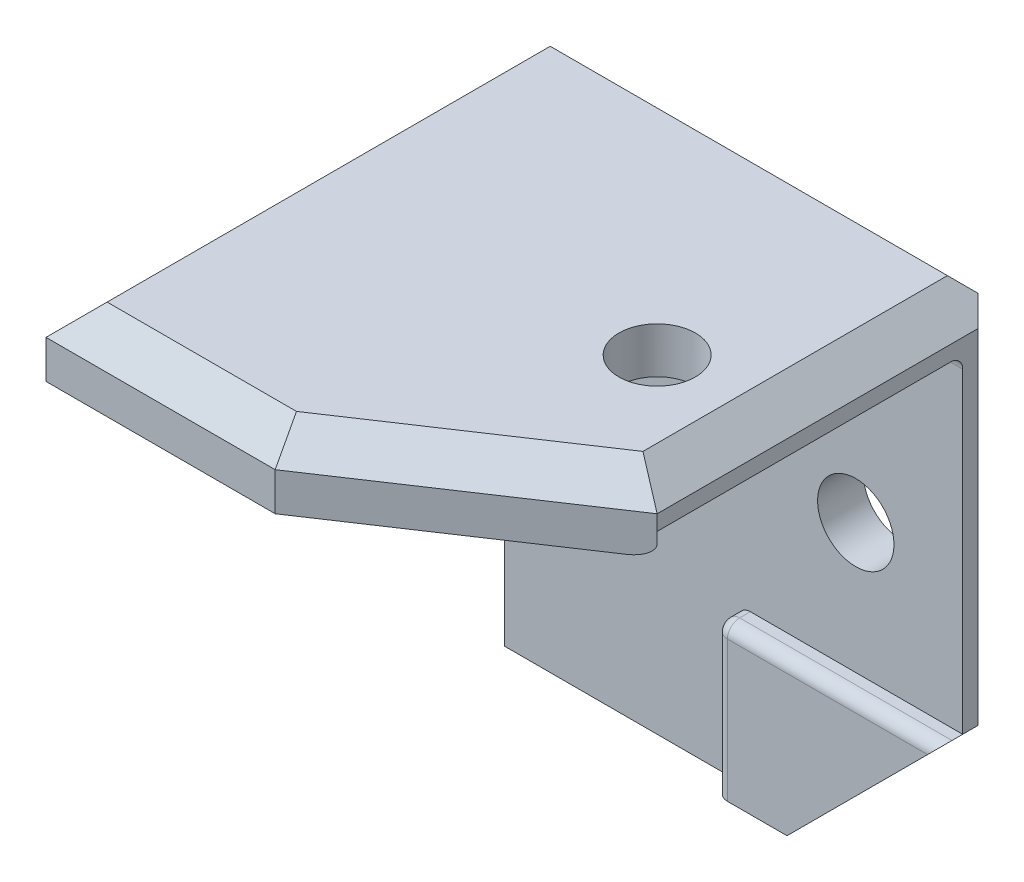
SolidWorks part; units mm, degrees
ref_plane "Front Plane" through (0, 0, 0) normal (0, 0, 1) x (1, 0, 0)
ref_plane "Top Plane" through (0, 0, 0) normal (0, 1, 0) x (1, 0, 0)
ref_plane "Right Plane" through (0, 0, 0) normal (1, 0, 0) x (0, 0, -1)
sketch "Sketch1" plane through (0, 0, 0) normal (0, 0, 1) x (1, 0, 0)
  line L0 (0, 0) -> (20, 0)
  line L1 (20, 0) -> (30, 10)
  line L2 (30, 10) -> (30, 30)
  line L3 (30, 30) -> (0, 30)
  line L4 (0, 30) -> (0, 0)
  dimension "D1" = 20
  dimension "D2" = 20
  dimension "D3" = 30
  dimension "D4" = 30
extrude "Boss-Extrude1" add sketch "Sketch1" along normal blind 3
sketch "Sketch2" plane through (0, 0, 3) normal (0, 0, 1) x (1, 0, 0)
  line L0 (15.3, 10) -> (30, 10)
  line L2 (0, 23.5) -> (15, 23.5)
  line L3 (15, 23.5) -> (15, 30)
  line L4 (15.3, 0) -> (15.3, 10)
  line L5 (0, 30) -> (0, 0)
  line L6 (0, 0) -> (20, 0)
  line L7 (20, 0) -> (30, 10)
  line L8 (30, 10) -> (30, 30)
  line L9 (30, 30) -> (0, 30)
  line L10 (0, 30) -> (0, 0)
  line L11 (0, 0) -> (20, 0)
  line L12 (20, 0) -> (30, 10)
  line L13 (30, 10) -> (30, 30)
  line L14 (30, 30) -> (0, 30)
  line M8 (0, 30) -> (0, 0)
  line M10 (20, 0) -> (30, 10)
  line M12 (30, 30) -> (0, 30)
  dimension "D2" = 15
  dimension "D3" = 6.5
  dimension "D4" = 15.3
  dimension "D1" = 0
extrude "Boss-Extrude2" add sketch "Sketch2" along normal blind 1.5 contours L2 L3 M12 M8 | M10 region at (20.5796, 5.8591, 3) region at (7.5, 26.75, 3)
sketch "Sketch3" plane through (0, 30, 0) normal (0, 1, 0) x (1, 0, 0)
  line L0 (0, -3) -> (0, -33)
  line L1 (0, -33) -> (15, -33)
  line L2 (30, -3) -> (30, -23)
  line L3 (30, -23) -> (15, -33)
  line L5 (0, -4.5) -> (0, 0) construction
  line L6 (30, -3) -> (30, 0) construction
  line L7 (30, 0) -> (0, 0) construction
  line L8 (30, -3) -> (30, 0)
  line L9 (30, 0) -> (0, 0)
  line L10 (0, 0) -> (0, -3)
  dimension "D1" = 33
  dimension "D2" = 15
  dimension "D3" = 20
extrude "Boss-Extrude3" add sketch "Sketch3" along normal blind 4.5
sketch "Sketch4" plane through (0, 30, 0) normal (0, -1, 0) x (1, 0, 0)
  line L0 (15, 4.5) -> (15, 23)
  line L1 (15, 23) -> (30, 23)
  line L7 (0, 4.5) -> (15, 4.5)
  line L8 (15, 4.5) -> (15, 3)
  line L9 (15, 3) -> (30, 3)
  line L10 (30, 3) -> (30, 23)
  line L11 (30, 23) -> (15, 33)
  line L12 (15, 33) -> (0, 33)
  line L13 (0, 33) -> (0, 4.5)
  line L14 (0, 4.5) -> (15, 4.5)
  line L15 (15, 4.5) -> (15, 3)
  line L16 (15, 3) -> (30, 3)
  line L17 (30, 3) -> (30, 23)
  line L18 (30, 23) -> (15, 33)
  line L19 (15, 33) -> (0, 33)
  line L20 (0, 33) -> (0, 4.5)
  line M11 (15, 4.5) -> (15, 3)
  line M12 (15, 3) -> (30, 3)
  line M13 (30, 3) -> (30, 23)
  dimension "D2" = 20
  dimension "D1" = 0
extrude "Cut-Extrude1" cut sketch "Sketch4" against normal blind 1.5 contours L1 L0 M11 M12 M13 region at (22.5, 30, 13)
fillet "Fillet1" radius 0.8 9 edges at (15, 30.75, 23) (22.5, 30, 23) (15, 30, 13.75) (15, 23.5, 3.75) (15, 26.75, 4.5) (7.5, 23.5, 4.5) (15.3, 10, 3.75) (15.3, 5, 4.5) (22.65, 10, 4.5)
chamfer "Chamfer1" distance 2 angle 45 1 edges at (15, 34.5, 0)
chamfer "Chamfer2" distance 2 angle 45 8 edges at (30, 21.25, 0) (25, 5, 0) (10, 0, 0) (0, 16.25, 0) (0, 34.5, 17.5) (30, 34.5, 12.5) (22.5, 34.5, 28) (7.5, 34.5, 33)
fillet "Fillet2" radius 0.8 1 edges at (22.5, 31.5, 3)
sketch "Sketch5" plane through (0, 0, 0) normal (0, 0, -1) x (-1, 0, 0)
  line L0 (-28, 34.5) -> (-2, 34.5) construction
  line L1 (-30, 10) -> (-30, 32.5) construction
  line L5 (-2, 32.5) -> (-28, 32.5)
  line L6 (-28, 32.5) -> (-28, 10.8284)
  line L7 (-28, 10.8284) -> (-19.1716, 2)
  line L8 (-19.1716, 2) -> (-2, 2)
  line L9 (-2, 2) -> (-2, 32.5)
  line L10 (-2, 32.5) -> (-28, 32.5)
  line L11 (-28, 32.5) -> (-28, 10.8284)
  line L12 (-28, 10.8284) -> (-19.1716, 2)
  line L13 (-19.1716, 2) -> (-2, 2)
  line L14 (-2, 2) -> (-2, 32.5)
  circle A0 centre (-23, 18.5) radius 2.5
  dimension "D3" = 5
  dimension "D2" = 16
  dimension "D4" = 7
  dimension "D1" = 0
extrude "Cut-Extrude2" cut sketch "Sketch5" against normal through all contours A0 region at (23, 18.5, 0)
sketch "Sketch6" plane through (0, 34.5, 0) normal (0, 1, 0) x (1, 0, 0)
  line L0 (2, 0) -> (28, 0) construction
  line L1 (30, -2) -> (30, -23) construction
  line L5 (28, -2) -> (2, -2)
  line L6 (2, -2) -> (2, -31)
  line L7 (2, -31) -> (14.3944, -31)
  line L8 (14.3944, -31) -> (28, -21.9296)
  line L9 (28, -21.9296) -> (28, -2)
  line L10 (28, -2) -> (2, -2)
  line L11 (2, -2) -> (2, -31)
  line L12 (2, -31) -> (14.3944, -31)
  line L13 (14.3944, -31) -> (28, -21.9296)
  line L14 (28, -21.9296) -> (28, -2)
  circle A0 centre (23, -16) radius 2.5
  dimension "D2" = 5
  dimension "D3" = 16
  dimension "D4" = 7
  dimension "D1" = 0
extrude "Cut-Extrude3" cut sketch "Sketch6" against normal through all contours A0 region at (23, 34.5, 16)
